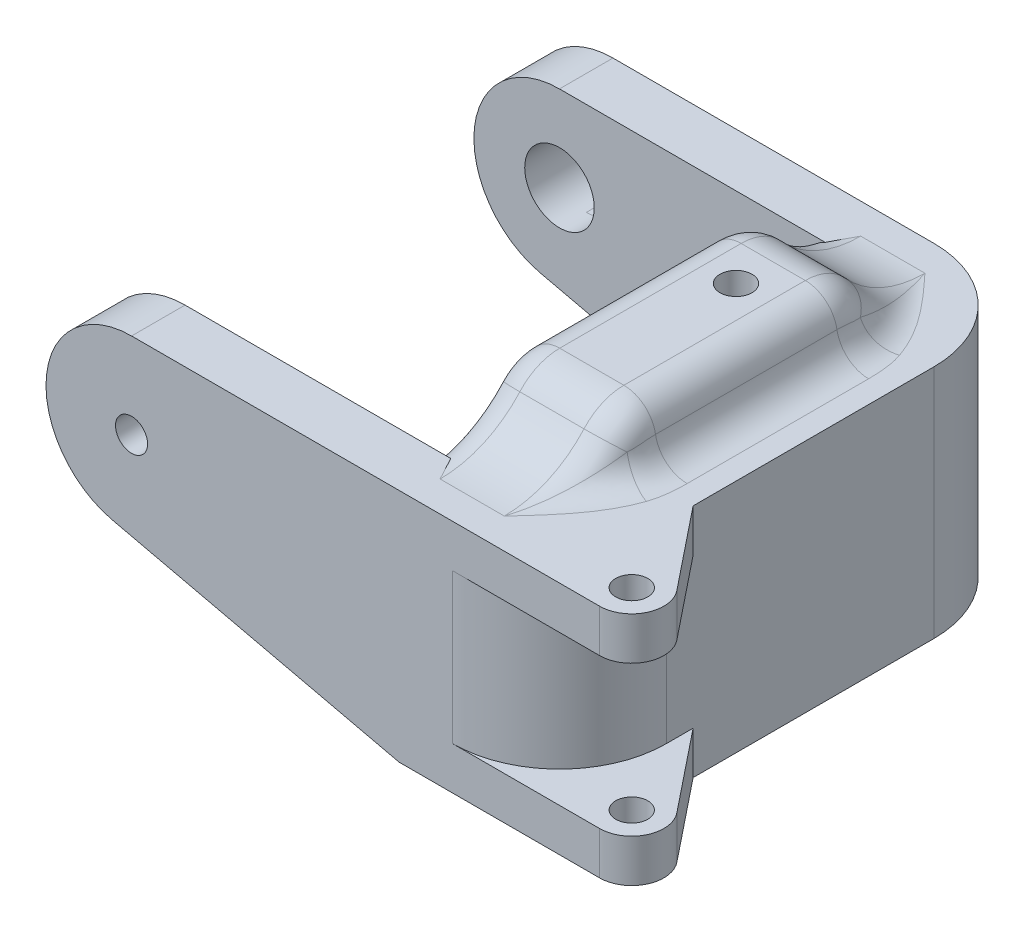
SolidWorks part; units mm, degrees
ref_plane "前视基准面" through (0, 0, 0) normal (0, 0, 1) x (1, 0, 0)
ref_plane "上视基准面" through (0, 0, 0) normal (0, 1, 0) x (1, 0, 0)
ref_plane "右视基准面" through (0, 0, 0) normal (1, 0, 0) x (0, 0, -1)
sketch "草图1" plane through (0, 0, 0) normal (0, 0, 1) x (1, 0, 0)
  line L0 (0.5609, -11) -> (27.3655, -4.7938)
  line L1 (0.5609, -11) -> (-14.4391, -11)
  line L3 (0.5609, 11) -> (-14.4391, 11)
  line L4 (-14.4391, -11) -> (-14.4391, 11)
  line L7 (0.5609, 11) -> (25.5609, 11)
  arc A1 (27.3655, -4.7938) -> (25.5609, 11) centre (25.5609, 3) ccw
  circle A2 centre (25.5609, 3) radius 1.5
  point P0 (0, 0)
  dimension "D4" = 8
  dimension "D5" = 3
  dimension "D1" = 22
  dimension "D2" = 15
  dimension "D3" = 25
extrude "凸台-拉伸1" add sketch "草图1" along normal blind 45
sketch "草图2" plane through (0, 11, 0) normal (0, 1, 0) x (1, 0, 0)
  line L0 (25.5609, 0) -> (-14.4391, 0) construction
  line L1 (-9.4391, -5) -> (42.9728, -5)
  line L2 (-9.4391, -5) -> (-9.4391, -40)
  line L3 (-9.4391, -40) -> (42.9728, -40)
  line L4 (42.9728, -5) -> (42.9728, -40)
  line L7 (-14.4391, -45) -> (-14.4391, 0) construction
  dimension "D1" = 35
  dimension "D2" = 52.4118
  dimension "D3" = 5
  dimension "D4" = 5
extrude "切除-拉伸1" cut sketch "草图2" against normal through all
sketch "草图4" plane through (0, -11, 0) normal (0, -1, 0) x (1, 0, 0)
  line L1 (-9.4391, 40) -> (2.5609, 40)
  line L2 (-9.4391, 40) -> (-9.4391, 33.5)
  line L3 (-9.4391, 33.5) -> (2.5609, 33.5)
  line L4 (2.5609, 40) -> (2.5609, 33.5)
  line L5 (-9.4391, 5) -> (2.5609, 5)
  line L6 (-9.4391, 5) -> (-9.4391, 11.5)
  line L7 (-9.4391, 11.5) -> (2.5609, 11.5)
  line L8 (2.5609, 5) -> (2.5609, 11.5)
  dimension "D1" = 6.5
  dimension "D2" = 12
  dimension "D3" = 6.5
  dimension "D4" = 12
extrude "凸台-拉伸2" add sketch "草图4" against normal blind 12
sketch "草图6" plane through (2.5609, 0, 0) normal (1, 0, 0) x (0, 0, -1)
  line L1 (-33.5, -11) -> (-40, -11)
  line L2 (-33.5, -11) -> (-33.5, -8.5)
  line L3 (-33.5, -8.5) -> (-40, -8.5)
  line L4 (-40, -11) -> (-40, -8.5)
  line L5 (-40, 1) -> (-40, -10.5369) construction
  line L7 (-11.5, -11) -> (-5, -11)
  line L8 (-11.5, -11) -> (-11.5, -8.5)
  line L9 (-11.5, -8.5) -> (-5, -8.5)
  line L10 (-5, -11) -> (-5, -8.5)
  line L11 (-5, -4.7938) -> (-5, -10.5369) construction
  dimension "D1" = 2.5
  dimension "D2" = 6.5
  dimension "D3" = 2.5
  dimension "D4" = 6.5
extrude "切除-拉伸2" cut sketch "草图6" against normal blind 12
sketch "草图7" plane through (0, -8.5, 0) normal (0, -1, 0) x (1, 0, 0)
  line L0 (-1009.4391, 22.5) -> (48990.5609, 22.5) construction
  line L1 (-9.4391, 5) -> (-9.4391, 40) construction
  line L2 (-9.4391, 33.5) -> (2.5609, 33.5) construction
  line L3 (-9.4391, 33.5) -> (-9.4391, 40) construction
  circle A0 centre (-3.4391, 36) radius 1
  circle A1 centre (-3.4391, 9) radius 1
  point P5 (-9.4391, 22.5)
  point P9 (-3.4391, 33.5)
  dimension "D1" = 2.5
  dimension "D2" = 6
extrude "切除-拉伸3" cut sketch "草图7" against normal blind 12
sketch "草图9" plane through (0, -11, 0) normal (0, -1, 0) x (1, 0, 0)
  line L0 (-14.4391, 45) -> (-18.1941, 45)
  line L1 (-20.536, 40.125) -> (-14.4391, 32.51)
  line L3 (-14.4391, 45) -> (-14.4391, 0) construction
  line L4 (-14.4391, 45) -> (-14.4391, 32.51)
  arc A0 (-18.1941, 45) -> (-20.536, 40.125) centre (-18.1941, 42) ccw
  circle A1 centre (-18.1941, 42) radius 1.5
  dimension "D1" = 3
  dimension "D3" = 6
extrude "凸台-拉伸3" add sketch "草图9" against normal blind 22
sketch "草图10" plane through (-14.4391, 0, 0) normal (-1, 0, 0) x (0, 0, 1)
  line L0 (40.125, 0) -> (-49959.875, 0) construction
  line L1 (40.125, 11) -> (40.125, -11) construction
  line L3 (50.1195, -7) -> (30.1305, -7)
  line L4 (50.1195, -7) -> (50.1195, 7)
  line L5 (50.1195, 7) -> (30.1305, 7)
  line L6 (30.1305, -7) -> (30.1305, 7)
  line L7 (50.1195, -7) -> (30.1305, 7) construction
  line L8 (50.1195, 7) -> (30.1305, -7) construction
  point P4 (40.125, 0)
  point P5 (40.125, 0)
  dimension "D1" = 14
  dimension "D2" = 19.9889
extrude "切除-拉伸4" cut sketch "草图10" along normal through all
sketch "草图12" plane through (0, 1, 0) normal (0, 1, 0) x (1, 0, 0)
  line L1 (-9.4391, -5) -> (2.5609, -5)
  line L2 (-9.4391, -5) -> (-9.4391, -11.5)
  line L3 (-9.4391, -11.5) -> (2.5609, -11.5)
  line L4 (2.5609, -5) -> (2.5609, -11.5)
  line L5 (-9.4391, -33.5) -> (2.5609, -33.5)
  line L6 (-9.4391, -33.5) -> (-9.4391, -40)
  line L7 (-9.4391, -40) -> (2.5609, -40)
  line L8 (2.5609, -33.5) -> (2.5609, -40)
  dimension "D1" = 6.5
  dimension "D2" = 12
  dimension "D3" = 6.5
  dimension "D4" = 12
extrude "切除-拉伸5" cut sketch "草图12" against normal blind 6
sketch "草图13" plane through (-9.4391, 0, 0) normal (1, 0, 0) x (0, 0, -1)
  line L1 (-40, 11) -> (-5, 11)
  line L2 (-40, 11) -> (-40, 7)
  line L3 (-40, 7) -> (-5, 7)
  line L4 (-5, 11) -> (-5, 7)
  line L5 (-5, -5) -> (-5, 11) construction
  dimension "D1" = 4
  dimension "D2" = 35
extrude "凸台-拉伸4" add sketch "草图13" along normal blind 12
sketch "草图14" plane through (0, 11, 0) normal (0, 1, 0) x (1, 0, 0)
  line L1 (-9.4391, -33.5) -> (2.5609, -33.5)
  line L2 (-9.4391, -33.5) -> (-9.4391, -11.5)
  line L3 (-9.4391, -11.5) -> (2.5609, -11.5)
  line L4 (2.5609, -33.5) -> (2.5609, -11.5)
  dimension "D1" = 22
  dimension "D2" = 12
extrude "凸台-拉伸5" add sketch "草图14" along normal blind 5
sketch "草图15" plane through (0, 7, 0) normal (0, -1, 0) x (1, 0, 0)
  line L1 (2.5609, 11.5) -> (-9.4391, 11.5)
  line L2 (2.5609, 11.5) -> (2.5609, 33.5)
  line L3 (2.5609, 33.5) -> (-9.4391, 33.5)
  line L4 (-9.4391, 11.5) -> (-9.4391, 33.5)
  dimension "D1" = 22
  dimension "D2" = 12
extrude "切除-拉伸6" cut sketch "草图15" against normal blind 3
fillet "圆角1" radius 10 2 edges at (-3.4391, 11, 11.5) (-3.4391, 11, 33.5)
fillet "圆角2" radius 5 2 edges at (-3.4391, 16, 11.5) (-3.4391, 16, 33.5)
fillet "圆角4" radius 5 2 edges at (-3.4391, 7, 11.5) (-3.4391, 7, 33.5)
sketch "草图16" plane through (0, 10, 0) normal (0, -1, 0) x (1, 0, 0)
  circle A0 centre (-3.4391, 17.5) radius 1.5
  dimension "D1" = 3
extrude "切除-拉伸7" cut sketch "草图16" against normal blind 10
fillet "圆角7" radius 3 5 edges at (-9.4391, 11.8713, 6.9222) (-9.4391, 15.5644, 11.9788) (-9.4391, 16, 22.5) (-9.4391, 15.5644, 33.0212) (-9.4391, 11.8713, 38.0778)
fillet "圆角8" radius 3 3 edges at (-8.9752, 11, 8.308) (-8.9752, 11, 36.692) (-9.4391, 11, 22.5)
sketch "草图17" plane through (0, 10, 0) normal (0, -1, 0) x (1, 0, 0)
  line L1 (-3.4391, 20.0981) -> (-5.6891, 18.799)
  line L2 (-5.6891, 18.799) -> (-5.6891, 16.201)
  line L3 (-5.6891, 16.201) -> (-3.4391, 14.9019)
  line L4 (-3.4391, 14.9019) -> (-1.1891, 16.201)
  line L5 (-1.1891, 16.201) -> (-1.1891, 18.799)
  line L6 (-1.1891, 18.799) -> (-3.4391, 20.0981)
  circle A0 centre (-3.4391, 17.5) radius 2.25 construction
  point P1 (-1.1891, 17.5)
  dimension "D1" = 4.5
extrude "切除-拉伸8" cut sketch "草图17" against normal blind 2
fillet "圆角9" radius 3 5 edges at (2.5609, 15.5644, 33.0212) (2.5609, 15.5644, 11.9788) (2.5609, 11.8713, 6.9222) (2.5609, 11.8713, 38.0778) (2.5609, 16, 22.5)
ref_plane "基准面2" through (-24.4391, 0, 0) normal (-1, 0, 0) x (0, 0, 1)
mirror "镜向2" about plane through (-24.4391, 0, 0) normal (-1, 0, 0) of bodies 118
delete or keep bodies "实体-删除/保留 2" type delete bodies bodies 118
fillet "圆角10" radius 10 2 edges at (-34.4391, 0, 0) (-34.4391, 0, 45)
sketch "草图18" plane through (0, 0, 0) normal (0, 0, -1) x (-1, 0, 0)
  circle A0 centre (74.4391, 3) radius 3.25
  dimension "D1" = 6.5
extrude "切除-拉伸9" cut sketch "草图18" against normal blind 10
sketch "草图19" plane through (0, 0, 0) normal (0, 0, -1) x (-1, 0, 0)
  line L0 (54.4391, 6.25) -> (74.4391, 6.25)
  line L1 (77.6891, 3) -> (49074.4391, 3) construction
  line L2 (54.4391, -0.25) -> (74.4391, -0.25)
  line L3 (-925.5609, 3) -> (51.1891, 3) construction
  arc A0 (74.4391, -0.25) -> (74.4391, 6.25) centre (74.4391, 3) ccw
  arc A1 (54.4391, 6.25) -> (54.4391, -0.25) centre (54.4391, 3) ccw
  dimension "D1" = 6.5
  dimension "D2" = 20
extrude "切除-拉伸10" cut sketch "草图19" against normal blind 2.5
